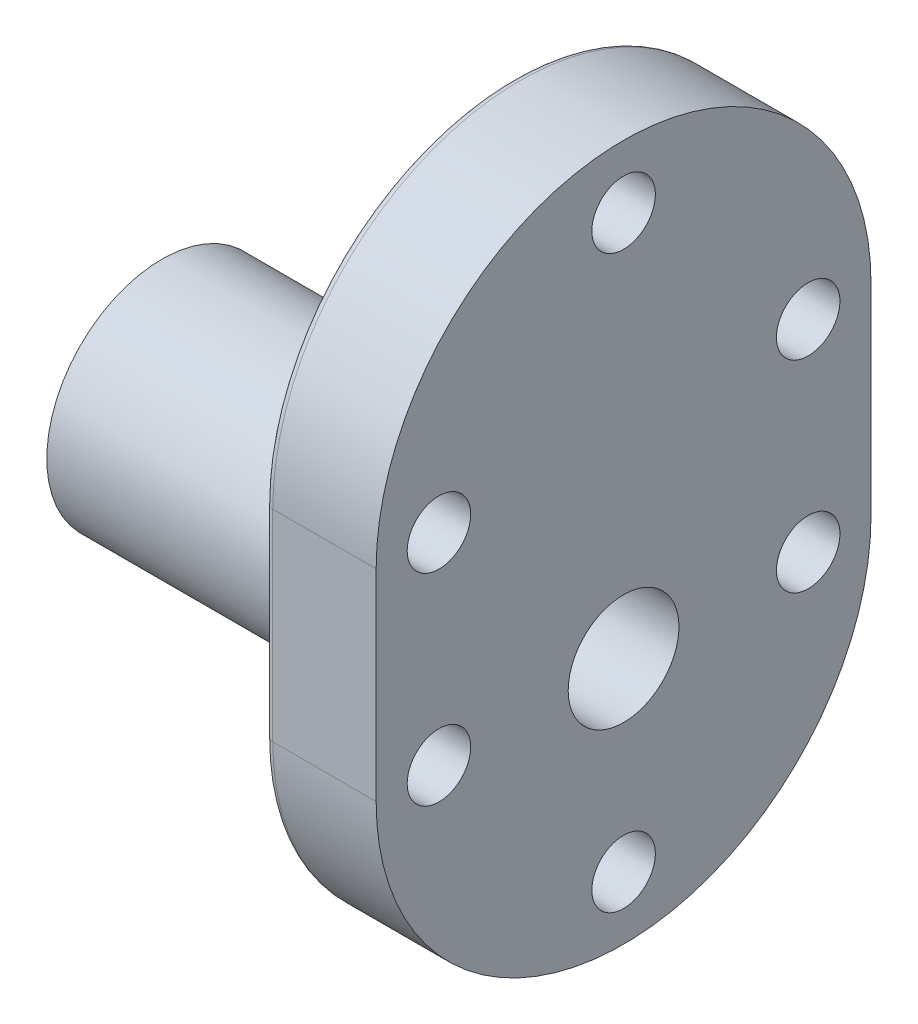
SolidWorks part; units mm, degrees
ref_plane "Front Plane" through (0, 0, 0) normal (0, 0, 1) x (1, 0, 0)
ref_plane "Top Plane" through (0, 0, 0) normal (0, 1, 0) x (1, 0, 0)
ref_plane "Right Plane" through (0, 0, 0) normal (1, 0, 0) x (0, 0, -1)
sketch "Sketch1" plane through (0, 0, 0) normal (1, 0, 0) x (0, 0, -1)
  line L0 (-85.1, 69.3) -> (-85.1, 0)
  line L1 (85.1, 69.3) -> (85.1, 0)
  arc A0 (-85.1, 0) -> (85.1, 0) centre (0, 0) ccw
  arc A1 (85.1, 69.3) -> (-85.1, 69.3) centre (0, 69.3) ccw
  dimension "D1" = 170.2
  dimension "D2" = 69.3
extrude "Boss-Extrude1" add sketch "Sketch1" against normal blind 38.1
sketch "Sketch2" plane through (-38.1, 0, 0) normal (-1, 0, 0) x (0, 0, 1)
  circle A0 centre (0, 0) radius 39.62
  dimension "D1" = 79.24
extrude "Boss-Extrude2" add sketch "Sketch2" along normal blind 120.65
hole_wizard "1/16 (1.25) Diameter Hole1" positions "3DSketch1" profile "Sketch3" hole size "1/16" standard "ANSI Inch"
sketch3d "3DSketch1"
  line L0 (-158.75, 0, 0) -> (-38.1, 0, 0) construction
  point P0 (-158.75, 0, 0)
sketch "Sketch3" plane through (-158.75, 0, 0) normal (0, 1, 0) x (0, 0, 1)
  line L0 (0, 0) -> (0, 76.2)
  line L1 (0, 76.2) -> (15.875, 71.9463)
  line L2 (15.875, 71.9463) -> (15.875, 0)
  line L5 (15.875, 0) -> (0, 0)
  line L10 (0, 76.2) -> (-15.875, 71.9463) construction
  line L11 (0, -6.35) -> (0, 107.95) construction
  dimension "Hole Dia." = 31.75
  dimension "Hole Depth" = 76.2
  dimension "Drill Angle" = 150
sketch "Sketch4" plane through (-158.75, 0, 0) normal (-1, 0, 0) x (0, 0, 1)
  circle A0 centre (0, 0) radius 19.05
  dimension "D1" = 38.1
extrude "Cut-Extrude1" cut sketch "Sketch4" against normal through all
fillet "Fillet1" radius 3.81 1 edges at (-38.1, 0, -39.62)
sketch "Sketch6" plane through (-38.1, 0, 0) normal (-1, 0, 0) x (0, 0, 1)
  line L0 (-85.1, 34.65) -> (85.1, 34.65) construction
  line L1 (-85.1, 0) -> (-85.1, 69.3) construction
  line L2 (85.1, 69.3) -> (85.1, 0) construction
  line L3 (0, 154.4) -> (0, 34.65) construction
  arc A0 (85.1, 69.3) -> (-85.1, 69.3) centre (0, 69.3) ccw construction
  circle A1 centre (0, 132.821) radius 10.922
  circle A2 centre (63.5, 69.321) radius 10.922
  circle A3 centre (-63.5, 69.321) radius 10.922
  circle A4 centre (63.5, -0.021) radius 10.922
  circle A5 centre (0, -63.521) radius 10.922
  circle A6 centre (-63.5, -0.021) radius 10.922
  dimension "D1" = 21.844
  dimension "D2" = 63.5
  dimension "D3" = 63.5
  dimension "D4" = 69.342
extrude "Cut-Extrude2" cut sketch "Sketch6" against normal through all
fillet "Fillet2" radius 2.54 4 edges at (-38.1, 34.65, -85.1) (-38.1, -85.1, 0) (-38.1, 34.65, 85.1) (-38.1, 154.4, 0)
hole_wizard "1/16 (2.5) Diameter Hole1" positions "3DSketch3" profile "Sketch8" hole size "1/16" standard "ANSI Inch"
sketch3d "3DSketch3"
  line L0 (0, 0, 0) -> (-158.75, 0, 0) construction
  point P0 (-158.75, 0, 0)
sketch "Sketch8" plane through (-158.75, 0, 0) normal (0, 1, 0) x (0, 0, 1)
  line L0 (0, 0) -> (0, 76.2)
  line L1 (0, 76.2) -> (31.75, 67.6926)
  line L2 (31.75, 67.6926) -> (31.75, 0)
  line L5 (31.75, 0) -> (0, 0)
  line L10 (0, 76.2) -> (-31.75, 67.6926) construction
  line L11 (0, -6.35) -> (0, 107.95) construction
  dimension "Hole Dia." = 63.5
  dimension "Hole Depth" = 76.2
  dimension "Drill Angle" = 150
